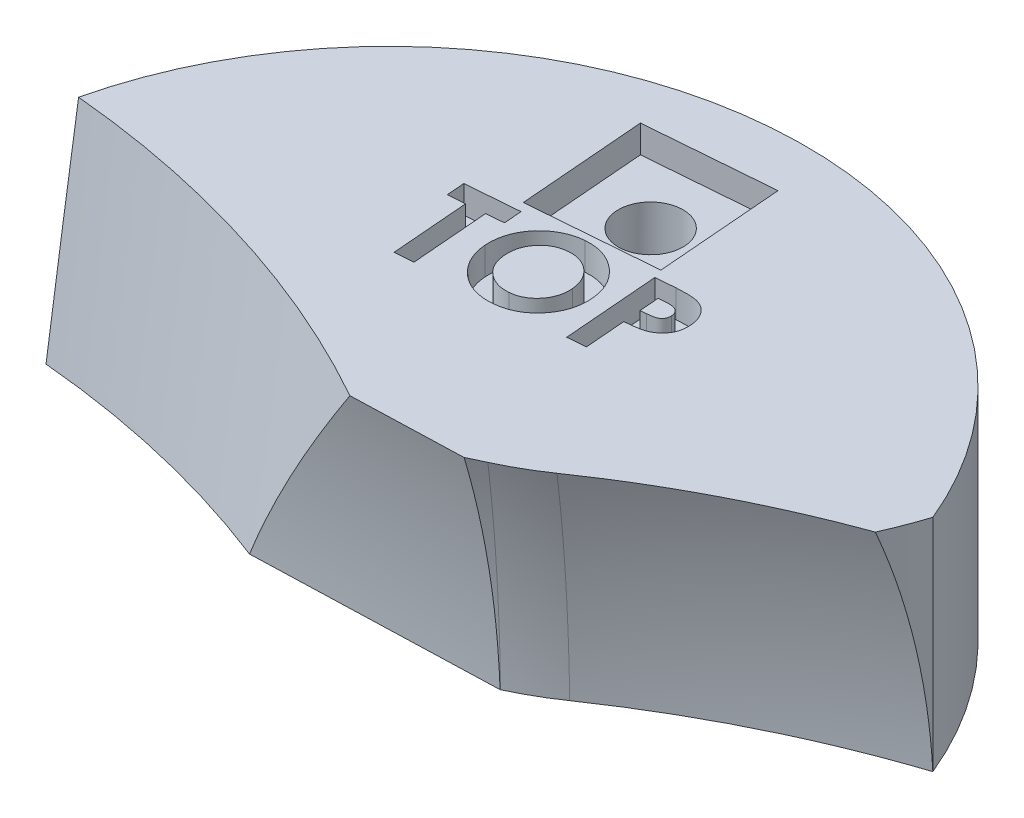
SolidWorks part; units mm, degrees
ref_plane "Front Plane" through (0, 0, 0) normal (0, 0, 1) x (1, 0, 0)
ref_plane "Top Plane" through (0, 0, 0) normal (0, 1, 0) x (1, 0, 0)
ref_plane "Right Plane" through (0, 0, 0) normal (1, 0, 0) x (0, 0, -1)
sketch "Sketch1" plane through (0, 0, 0) normal (0, 1, 0) x (1, 0, 0)
  circle A0 centre (0, 0) radius 16
  dimension "D1" = 32
extrude "Boss-Extrude1" add sketch "Sketch1" along normal blind 8 contours A0
sketch "Sketch2" plane through (0, 8, 0) normal (0, 1, 0) x (1, 0, 0)
  circle A0 centre (0, 0) radius 2.32
  dimension "D1" = 4.64
extrude "Cut-Extrude1" cut sketch "Sketch2" against normal blind 1
sketch "Sketch3" plane through (0, 7, 0) normal (0, 1, 0) x (1, 0, 0)
  circle A0 centre (0, 0) radius 1.175
  dimension "D1" = 2.35
extrude "Cut-Extrude2" cut sketch "Sketch3" against normal through all
sketch "Sketch5" plane through (0, 0, 0) normal (0, -1, 0) x (1, 0, 0)
  circle A0 centre (0, 0) radius 2.3
  dimension "D1" = 4.6
extrude "Cut-Extrude3" cut sketch "Sketch5" against normal blind 2
ref_point "Point1"
ref_plane "Plane1" through (0, -1.3, 0) normal (0, 1, 0) x (1, 0, 0)
sketch "Sketch7" plane through (0, -1.3, 0) normal (0, 1, 0) x (1, 0, 0)
  line L0 (26.088, -3.1982) -> (26.088, -72.9782)
  circle A2 centre (26.088, -38.0882) radius 34.89
  circle A3 centre (26.088, -38.0882) radius 34.89
  point P2 (19.4807, -7.9991)
  dimension "D1" = 0.6
revolve "Cut-Revolve1" cut sketch "Sketch7" angle 360 about L0 region at (11.2802, -1.3, 38.0882)
sketch "Sketch16" plane through (0, -1.3, 0) normal (0, 1, 0) x (1, 0, 0)
  line L0 (26.088, -38.0882) -> (0, 0) construction
  line L1 (6.372, -9.303) -> (16.6558, -4.4974) construction
  line L2 (6.372, -9.303) -> (15.7371, -2.8885) construction
  line L3 (0, 0) -> (19.5446, -41.8247) construction
  line L4 (19.5446, -41.8247) -> (26.088, -38.0882)
  line L5 (13.1999, -76.133) -> (25.8893, -7.5164)
  circle A1 centre (0, 0) radius 11.276
  circle A2 centre (26.088, -38.0882) radius 34.89
  circle A3 centre (26.088, -38.0882) radius 34.89
  arc A4 (14.6327, -6.4718) -> (0.7471, -15.9825) centre (0, 0) ccw construction
  circle A5 centre (19.5446, -41.8247) radius 34.89
  point P16 (0, 0)
  dimension "D2" = 22.5519
  dimension "D3" = 9.362
  dimension "D4" = 9.362
  dimension "D1" = 0.6
revolve "Cut-Revolve10" cut sketch "Sketch16" angle 360 about L5 region at (8.071, -1.3, 35.7845) region at (12.972, -1.3, 73.3745)
revolve "Cut-Revolve12" cut sketch "Sketch16<4>" angle 360 about L4 region at (5.5971, -1.3, 9.8017)
sketch "Sketch16<4>" plane through (0, -1.3, 0) normal (0, 1, 0) x (1, 0, 0) same geometry as "Sketch16"
sketch "Sketch17" plane through (0, -1.3, 0) normal (0, 1, 0) x (1, 0, 0)
  line L0 (-16.7976, -43.0016) -> (0, 0) construction
  line L1 (0, 0) -> (19.5446, -41.8247) construction
  circle A0 centre (-16.7976, -43.0016) radius 34.89
  arc A1 (5.4019, -11.3156) -> (-1.8628, -15.8912) centre (19.5446, -41.8247) ccw construction
  arc A2 (5.4019, -11.3156) -> (-1.8628, -15.8912) centre (19.5446, -41.8247) ccw
  circle A3 centre (19.5446, -41.8247) radius 34.89 construction
  point P5 (1.6229, -13.3706)
  point P10 (-16.7976, -43.0016)
  dimension "D1" = 46.384
extrude "Cut-Extrude6" cut sketch "Sketch17" along normal through all contours A0 region at (-16.7976, -1.3, 43.0016)
sketch "Sketch18" plane through (0, -1.3, 0) normal (0, 1, 0) x (1, 0, 0)
  line L0 (-4.1028, -10.5031) -> (4.7737, -10.2156)
  line L1 (0, 0) -> (19.5446, -41.8247) construction
  line L2 (-16.7976, -43.0016) -> (0, 0) construction
  line L3 (-16.7976, -43.0016) -> (19.5446, -41.8247)
  line L4 (19.5446, -41.8247) -> (4.7737, -10.2156)
  line L5 (-4.1028, -10.5031) -> (-16.7976, -43.0016)
  circle A2 centre (19.5446, -41.8247) radius 34.89 construction
  circle A3 centre (-16.7976, -43.0016) radius 34.89 construction
revolve "Cut-Revolve13" cut sketch "Sketch18" angle 360 about L3
sketch "Sketch19" plane through (0, 8, 0) normal (0, 1, 0) x (1, 0, 0)
  line L0 (-0.2619, 2.3052) -> (-0.4891, 4.3052)
  line L1 (0, 0) -> (-0.2619, 2.3052) construction
  line L2 (0, 0) -> (1.2194, -10.7327) construction
  arc A0 (15.211, -4.9625) -> (-13.7099, -8.2485) centre (0, 0) ccw construction
  arc A1 (15.211, -4.9625) -> (-13.7099, -8.2485) centre (0, 0) ccw
  arc A2 (-13.7099, -8.2485) -> (15.211, -4.9625) centre (1.2194, -10.7327) cw
  circle A3 centre (0, 0) radius 2.32 construction
  arc M7 (14.6327, -6.4718) -> (-13.7099, -8.2485) centre (0, 0) ccw
  dimension "D1" = 2
extrude "Cut-Extrude7" cut sketch "Sketch19" against normal through all contours A2 M7 region at (-0.7707, 8, -6.7829)
chamfer "Chamfer1" distance 1 distance2 8 1 edges at (-7.2928, 8, 9.4312) first distance on face at (0, 8, 2.32)
sketch "Sketch20" plane through (0, 8, 0) normal (0, 1, 0) x (1, 0, 0)
  line L0 (15.211, -4.9625) -> (-13.512, -7.2623) construction
  text T0 "<b>TOP</b>"
extrude "Cut-Extrude8" cut sketch "Sketch20" against normal blind 1
sketch "Sketch21" plane through (0, 8, 0) normal (0, 1, 0) x (1, 0, 0)
  line L0 (-2.2346, -6.359) -> (-2.9063, -6.413) construction
  line L1 (-2.1267, -2.4984) -> (2.4984, -2.1267)
  line L2 (-2.1267, -2.4984) -> (-2.4984, 2.1267)
  line L3 (-2.4984, 2.1267) -> (2.1267, 2.4984)
  line L4 (2.4984, -2.1267) -> (2.1267, 2.4984)
  line L5 (-2.1267, -2.4984) -> (2.1267, 2.4984) construction
  line L6 (-2.4984, 2.1267) -> (2.4984, -2.1267) construction
  circle A0 centre (0, 0) radius 2.32 construction
  point P0 (0, 0)
  circle M9 centre (0, 0) radius 2.32
extrude "Cut-Extrude10" cut sketch "Sketch21" against normal up to surface (1 mm away) contours L3 L2 M9 | L4 L3 M9 | L1 L4 M9 | L2 L1 M9 region at (-1.6516, 8, 1.9403) region at (1.9403, 8, 1.6516) region at (-1.9403, 8, -1.6516) region at (1.6516, 8, -1.9403) up to face at (0, 7, 1.175)
